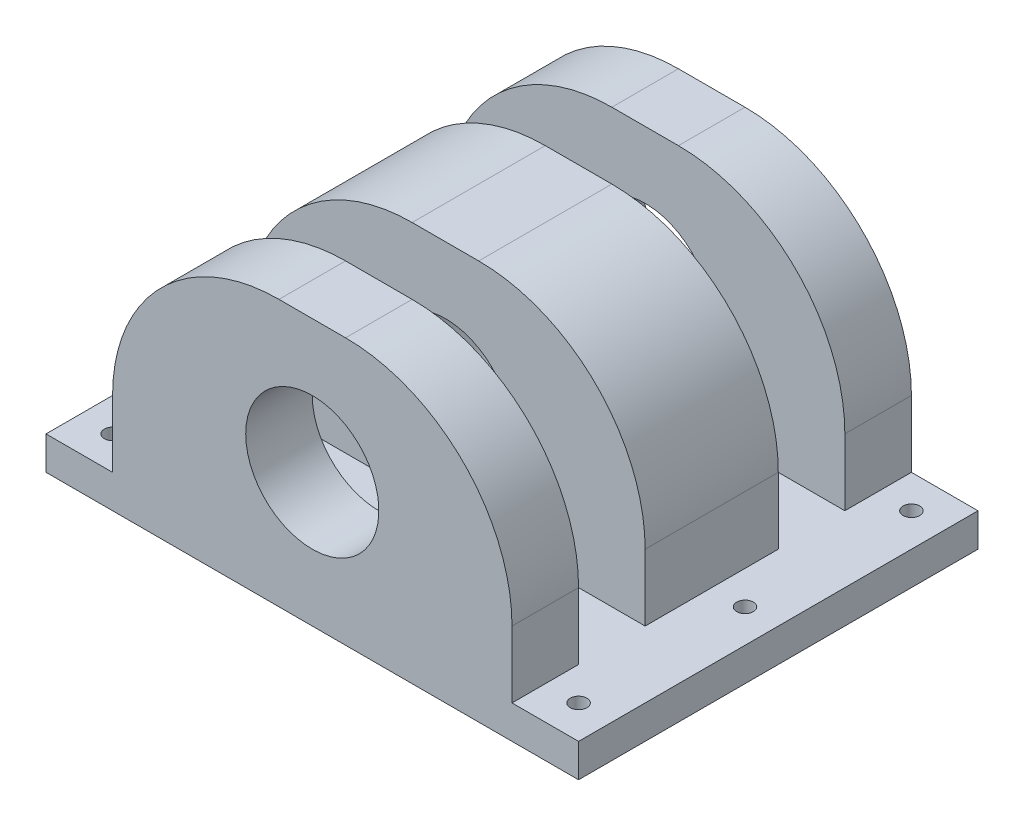
SolidWorks part; units mm, degrees
ref_plane "Front Plane" through (0, 0, 0) normal (0, 0, 1) x (1, 0, 0)
ref_plane "Top Plane" through (0, 0, 0) normal (0, 1, 0) x (1, 0, 0)
ref_plane "Right Plane" through (0, 0, 0) normal (1, 0, 0) x (0, 0, -1)
sketch "Sketch1" plane through (0, 0, 0) normal (0, 0, 1) x (1, 0, 0)
  line L1 (-76.2, -50.8) -> (76.2, -50.8)
  line L2 (-76.2, -38.1) -> (-76.2, -12.7)
  line L3 (-12.7, 50.8) -> (12.7, 50.8)
  line L4 (76.2, -38.1) -> (76.2, -12.7)
  line L5 (-76.2, -50.8) -> (76.2, 50.8) construction
  line L6 (-76.2, 50.8) -> (76.2, -50.8) construction
  line L7 (-76.2, -50.8) -> (-101.6, -50.8)
  line L9 (-76.2, -38.1) -> (-101.6, -38.1)
  line L10 (-101.6, -50.8) -> (-101.6, -38.1)
  line L11 (76.2, -50.8) -> (101.6, -50.8)
  line L13 (76.2, -38.1) -> (101.6, -38.1)
  line L14 (101.6, -50.8) -> (101.6, -38.1)
  arc A0 (76.2, -12.7) -> (12.7, 50.8) centre (12.7, -12.7) ccw
  arc A1 (-12.7, 50.8) -> (-76.2, -12.7) centre (-12.7, -12.7) ccw
  circle A2 centre (0, 0) radius 25.4
  point P0 (0, 0)
  dimension "D3" = 63.5
  dimension "D8" = 50.8
  dimension "D1" = 152.4
  dimension "D2" = 101.6
  dimension "D4" = 12.7
  dimension "D5" = 12.7
  dimension "D6" = 25.4
  dimension "D7" = 25.4
extrude "Boss-Extrude1" add sketch "Sketch1" along normal blind 152.4
sketch "Sketch3" plane through (0, 0, 0) normal (1, 0, 0) x (0, 0, -1)
  line L0 (-152.4, -38.1) -> (0, -38.1) construction
  line L1 (-127, -38.1) -> (-101.6, -38.1)
  line L2 (-127, -38.1) -> (-127, 50.8)
  line L3 (-127, 50.8) -> (-101.6, 50.8)
  line L4 (-101.6, -38.1) -> (-101.6, 50.8)
  line L5 (-152.4, 50.8) -> (0, 50.8) construction
  line L6 (-152.4, 50.8) -> (-152.4, -12.7) construction
  line L7 (-50.8, -38.1) -> (-25.4, -38.1)
  line L8 (-50.8, -38.1) -> (-50.8, 50.8)
  line L9 (-50.8, 50.8) -> (-25.4, 50.8)
  line L10 (-25.4, -38.1) -> (-25.4, 50.8)
  dimension "D1" = 25.4
  dimension "D2" = 25.4
  dimension "D3" = 50.8
  dimension "D4" = 25.4
extrude "Cut-Extrude1" cut sketch "Sketch3" against normal through all both and the other way through all
sketch "Sketch4" plane through (0, -38.1, 0) normal (0, 1, 0) x (1, 0, 0)
  line L0 (-101.6, -152.4) -> (-101.6, 0) construction
  line L1 (101.6, -152.4) -> (101.6, 0) construction
  line L2 (-76.2, 0) -> (-101.6, 0) construction
  point P0 (-88.9, -12.7)
  point P1 (-88.9, -76.2)
  point P2 (-88.9, -139.7)
  point P3 (88.9, -12.7)
  point P4 (88.9, -76.2)
  point P5 (88.9, -139.7)
  point P12 (0, 0)
  point P13 (0, 0)
  point P14 (0, 0)
  point P15 (0, 0)
  dimension "D1" = 12.7
  dimension "D2" = 12.7
  dimension "D3" = 12.7
  dimension "D4" = 63.5
  dimension "D5" = 63.5
hole_wizard "1/4 (0.25) Diameter Hole1" positions "Sketch5" profile "Sketch6" hole size "1/4" standard "ANSI Inch" end condition through all
sketch "Sketch5" plane through (0, -38.1, 0) normal (0, 1, 0) x (1, 0, 0)
  point P0 (-88.9, -76.2)
  point P3 (-88.9, -12.7)
  point P6 (-88.9, -139.7)
  point P9 (88.9, -12.7)
  point P12 (88.9, -76.2)
  point P15 (88.9, -139.7)
sketch "Sketch6" plane through (-88.9, -38.1, 76.2) normal (1, 0, 0) x (0, 0, 1)
  line L0 (0, 0) -> (0, 12.7)
  line L1 (0, 12.7) -> (3.175, 12.7)
  line L2 (3.175, 12.7) -> (3.175, 0)
  line L5 (3.175, 0) -> (0, 0)
  line L11 (0, -6.35) -> (0, 107.95) construction
  dimension "Thru Hole Dia." = 6.35
  dimension "Thru Hole Depth" = 12.7
